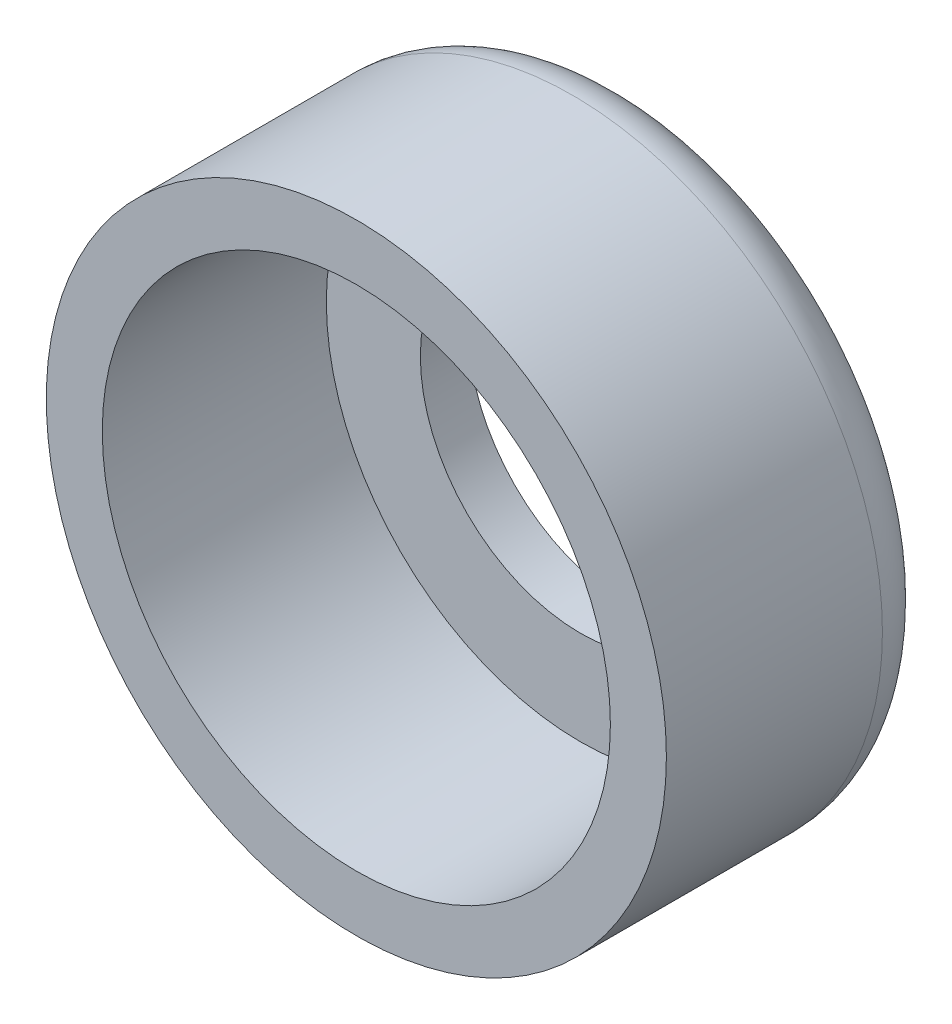
SolidWorks part; units mm, degrees
ref_plane "Front Plane" through (0, 0, 0) normal (1, 0, 0) x (0, 1, 0)
ref_plane "Top Plane" through (0, 0, 0) normal (0, 0, 1) x (0, 1, 0)
ref_plane "Right Plane" through (0, 0, 0) normal (0, 1, 0) x (-1, 0, 0)
ref_axis "x axis" through (-88.99, 0, 0) along (1, 0, 0)
ref_axis "y xxis" through (0, 88.99, 0) along (0, -1, 0)
ref_axis "z axis" through (0, 0, 55) along (0, 0, -1)
sketch "Sketch1" plane through (0, 0, 0) normal (0, 0, 1) x (0, 1, 0)
  circle A0 centre (0, 0) radius 2
  circle A1 centre (0, 0) radius 3.875
  circle A2 centre (0, 0) radius 3.175 construction
  dimension "D1" = 6.35
  dimension "D2" = 0.7
  dimension "D3" = 4
extrude "Boss-Extrude1" add sketch "Sketch1" along normal blind 0.6
sketch "Sketch2" plane through (0, 0, 0.6) normal (0, 0, 1) x (1, 0, 0)
  circle A0 centre (0, 0) radius 3.175
  circle A1 centre (0, 0) radius 3.875
  circle A2 centre (0, 0) radius 3.175 construction
  circle A3 centre (0, 0) radius 3.875 construction
extrude "Boss-Extrude2" add sketch "Sketch2" along normal blind 2.8
fillet "Fillet1" radius 0.7 1 edges at (3.875, 0, 0)
